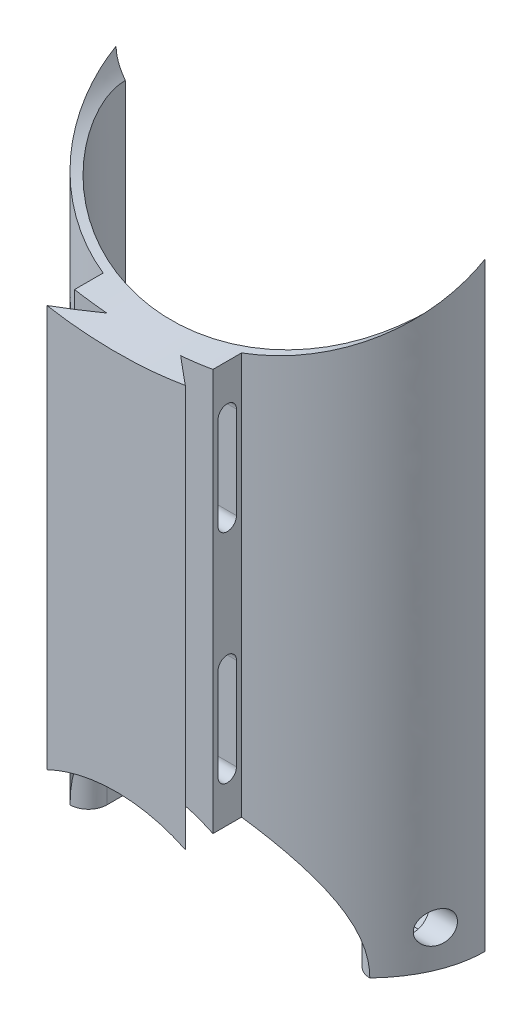
SolidWorks part; units mm, degrees
material "PLA"
ref_plane "Front Plane" through (0, 0, 0) normal (0, 0, 1) x (1, 0, 0)
ref_plane "Top Plane" through (0, 0, 0) normal (0, 1, 0) x (1, 0, 0)
ref_plane "Right Plane" through (0, 0, 0) normal (1, 0, 0) x (0, 0, -1)
sketch "Sketch1" plane through (0, 0, 0) normal (0, 1, 0) x (1, 0, 0)
  ellipse E0 centre (0, 0) end of major axis (25.4, 0) minor radius 19.05
  dimension "D1" = 50.8
  dimension "D2" = 38.1
extrude "Boss-Extrude1" add sketch "Sketch1" along normal blind 82.55 contours E0
shell "Shell1" thickness 1.27 removed face at (25.4, 82.55, 0) removed face at (25.4, 0, 0)
sketch "Sketch3" plane through (0, 0, 0) normal (0, 0, 1) x (1, 0, 0)
  line L1 (29.1836, -15.0653) -> (-40.8926, -15.0653)
  line L2 (29.1836, -15.0653) -> (29.1836, 110.7022)
  line L3 (29.1836, 110.7022) -> (-40.8926, 110.7022)
  line L4 (-40.8926, -15.0653) -> (-40.8926, 110.7022)
extrude "Cut-Extrude1" cut sketch "Sketch3" against normal up to surface up to face at (25.4, 82.55, 0)
ref_plane "Plane4" through (0, 0, 19.05) normal (0, 0, 1) x (1, 0, 0)
sketch "Sketch4" plane through (0, 0, 19.05) normal (0, 0, 1) x (1, 0, 0)
  line L1 (9.525, 82.55) -> (-9.525, 82.55)
  line L2 (9.525, 82.55) -> (9.525, 0)
  line L3 (9.525, 0) -> (-9.525, 0)
  line L4 (-9.525, 82.55) -> (-9.525, 0)
  line L6 (25.4, 82.55) -> (25.4, 0) construction
  line L7 (-25.4, 0) -> (25.4, 0) construction
  line L8 (25.4, 82.55) -> (-25.4, 82.55) construction
  dimension "D1" = 19.05
  dimension "D4" = 15.875
extrude "Boss-Extrude2" add sketch "Sketch4" against normal up to surface up to face at (0, 41.275, 9.525)
sketch "Sketch6" plane through (0, 0, 19.05) normal (0, 0, 1) x (1, 0, 0)
  line L4 (-9.525, 0) -> (9.525, 0)
  line L5 (9.525, 0) -> (9.525, 82.55)
  line L6 (9.525, 82.55) -> (-9.525, 82.55)
  line L7 (-9.525, 82.55) -> (-9.525, 0)
  line L8 (-9.525, 0) -> (9.525, 0)
  line L9 (9.525, 0) -> (9.525, 82.55)
  line L10 (9.525, 82.55) -> (-9.525, 82.55)
  line L11 (-9.525, 82.55) -> (-9.525, 0)
  dimension "D1" = 0
extrude "Boss-Extrude4" add sketch "Sketch6" along normal blind 6.35
sketch "Sketch7" plane through (0, 0, 0) normal (0, -1, 0) x (1, 0, 0)
  line L0 (-9.525, 25.4) -> (-5.08, 21.59)
  line L1 (9.525, 25.4) -> (5.08, 21.59)
  line L2 (-5.08, 21.59) -> (-9.525, 21.59)
  line L3 (-9.525, 17.6598) -> (-9.525, 25.4) construction
  line L4 (-9.525, 21.59) -> (-9.525, 25.4)
  line L5 (5.08, 21.59) -> (9.525, 21.59)
  line L6 (9.525, 17.6598) -> (9.525, 25.4) construction
  line L7 (9.525, 21.59) -> (9.525, 25.4)
  line L8 (-9.525, 25.4) -> (9.525, 25.4) construction
  dimension "D2" = 3.81
  dimension "D3" = 10.16
extrude "Cut-Extrude2" cut sketch "Sketch7" against normal through all
sketch "Sketch8" plane through (0, 0, 19.05) normal (0, 0, 1) x (1, 0, 0)
  line L0 (9.525, 82.55) -> (-9.525, 82.55) construction
  line L1 (-9.525, 82.55) -> (-25.4, 82.55) construction
  ellipse E0 centre (0, 0) end of major axis (-20.6375, 0) minor radius 19.05
  ellipse E1 centre (0, 82.55) end of major axis (25.4, 82.55) minor radius 11.1125
  dimension "D1" = 38.1
  dimension "D2" = 41.275
  dimension "D3" = 22.225
extrude "Cut-Extrude3" cut sketch "Sketch8" against normal through all both and the other way through all
sketch "Sketch10" plane through (9.525, 0, 0) normal (1, 0, 0) x (0, 0, -1)
  line L0 (-19.6215, 23.2496) -> (-19.6215, 35.9496) construction
  line L2 (-20.8915, 23.2496) -> (-20.8915, 35.9496)
  line L3 (-18.3515, 23.2496) -> (-18.3515, 35.9496)
  line L4 (-17.6598, 16.8996) -> (-21.59, 16.8996) construction
  line L6 (-21.59, 72.2484) -> (-21.59, 16.8996) construction
  line L7 (-19.6215, 53.1984) -> (-19.6215, 65.8984) construction
  line L8 (-20.8915, 53.1984) -> (-20.8915, 65.8984)
  line L9 (-18.3515, 53.1984) -> (-18.3515, 65.8984)
  line L10 (-21.59, 72.2484) -> (-17.6598, 72.2484) construction
  arc A0 (-20.8915, 23.2496) -> (-18.3515, 23.2496) centre (-19.6215, 23.2496) ccw
  arc A1 (-18.3515, 35.9496) -> (-20.8915, 35.9496) centre (-19.6215, 35.9496) ccw
  arc A2 (-20.8915, 53.1984) -> (-18.3515, 53.1984) centre (-19.6215, 53.1984) ccw
  arc A3 (-18.3515, 65.8984) -> (-20.8915, 65.8984) centre (-19.6215, 65.8984) ccw
  point P4 (-19.6215, 29.5996)
  point P13 (-19.6215, 59.5484)
  point P18 (0, 0)
  point P19 (0, 0)
  dimension "D3" = 1.27
  dimension "D6" = 1.27
  dimension "D1" = 12.7
  dimension "D2" = 12.7
  dimension "D4" = 1.9685
  dimension "D5" = 12.7
  dimension "D7" = 12.7
extrude "Cut-Extrude4" cut sketch "Sketch10" against normal through all
ref_plane "Plane7" through (20.6375, 0, 0) normal (1, 0, 0) x (0, 0, -1)
ref_plane "Plane8" through (18.0975, 0, 0) normal (1, 0, 0) x (0, 0, -1)
sketch "Sketch14" plane through (18.0975, 0, 0) normal (1, 0, 0) x (0, 0, -1)
  line L1 (-11.1054, 0) -> (0, 0)
  line L2 (-11.1054, 0) -> (-11.1054, 10.16)
  line L3 (-11.1054, 10.16) -> (0, 10.16)
  line L4 (0, 0) -> (0, 10.16)
  dimension "D1" = 10.16
extrude "Boss-Extrude7" add sketch "Sketch14" along normal up to body separate body
sketch "Sketch15" plane through (18.0975, 0, 0) normal (-1, 0, 0) x (0, 0, 1)
  line L2 (11.1054, 10.16) -> (11.1054, 0) construction
  line L3 (11.1054, 0) -> (0, 0) construction
  circle A0 centre (5.5555, 5.08) radius 2.159
  point P2 (0, 0)
  point P6 (0, 0)
  dimension "D1" = 4.318
  dimension "D2" = 5.5499
  dimension "D3" = 5.08
extrude "Cut-Extrude7" cut sketch "Sketch15" against normal through all
sketch "Sketch16" plane through (18.0975, 0, 0) normal (-1, 0, 0) x (0, 0, 1)
  line L0 (0, 10.16) -> (11.1054, 10.16) construction
  line L1 (7.5719, 1.5875) -> (9.5883, 5.08)
  line L2 (9.5883, 5.08) -> (7.5719, 8.5725)
  line L3 (7.5719, 8.5725) -> (3.5391, 8.5725)
  line L4 (3.5391, 8.5725) -> (1.5227, 5.08)
  line L5 (1.5227, 5.08) -> (3.5391, 1.5875)
  line L6 (3.5391, 1.5875) -> (7.5719, 1.5875)
  circle A0 centre (5.5555, 5.08) radius 3.4925 construction
  dimension "D1" = 6.985
extrude "Cut-Extrude8" cut sketch "Sketch16" against normal blind 3.048
mirror "Mirror5" about plane through (0, 0, 0) normal (1, 0, 0) of "Cut-Extrude7", "Boss-Extrude7", "Cut-Extrude8"
fillet "Fillet2" radius 2.54 2 edges at (18.0975, 5.08, 11.1054) (-18.0975, 5.08, 11.1054)
